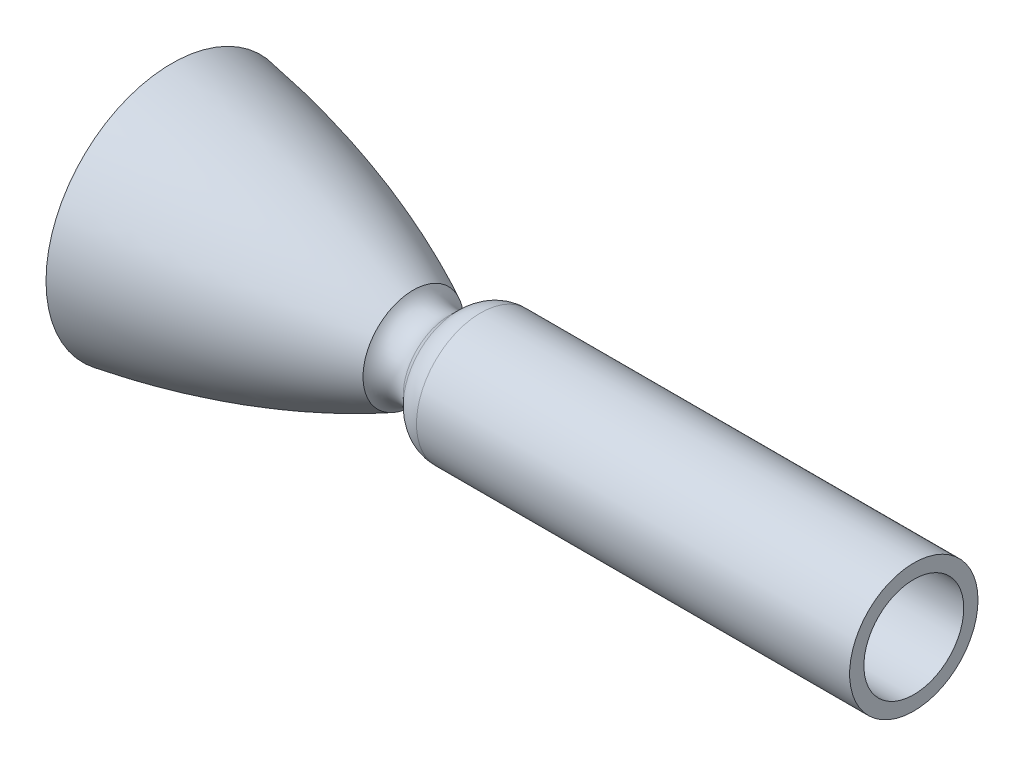
SolidWorks part; units mm, degrees
ref_plane "Front Plane" through (0, 0, 0) normal (0, 0, 1) x (1, 0, 0)
ref_plane "Top Plane" through (0, 0, 0) normal (0, 1, 0) x (1, 0, 0)
ref_plane "Right Plane" through (0, 0, 0) normal (1, 0, 0) x (0, 0, -1)
sketch "Sketch1" plane through (0, 0, 0) normal (0, 0, 1) x (1, 0, 0)
  line L0 (272.3324, 28) -> (29.4035, 28)
  line L1 (22.3324, 25.0711) -> (17.4121, 20.1508)
  line L3 (0, 0) -> (-234.9488, 0) construction
  line L8 (272.3324, 36) -> (29.4035, 36)
  line L12 (16.6756, 30.7279) -> (11.7553, 25.8076)
  line L13 (272.3324, 28) -> (272.3324, 36)
  line L14 (-145.1317, 62.6099) -> (-143.8678, 70.5094)
  arc A0 (29.4035, 28) -> (22.3324, 25.0711) centre (29.4035, 18) ccw
  arc A4 (29.4035, 36) -> (16.6756, 30.7279) centre (29.4035, 18) ccw
  arc A7 (-8.4641, 28.1148) -> (-8.4641, 28.1148) centre (-8.4641, 28.1148) ccw
  arc A8 (11.7553, 25.8076) -> (-8.4641, 28.1148) centre (2.5629, 35) cw construction
  arc A9 (-8.4641, 28.1148) -> (11.7553, 25.8076) centre (2.5629, 35) ccw
  arc A10 (-0.2556, 14.19) -> (0, 14.6541) centre (2.9733, 12.7139) cw construction
  arc A11 (17.4121, 20.1508) -> (-0.2556, 14.19) centre (2.5629, 35) cw construction
  arc A12 (17.4121, 20.1508) -> (2.5629, 14) centre (2.5629, 35) cw
  arc A13 (2.5629, 14) -> (0, 14.6541) centre (2.5629, 19.348) cw
  spline S0 degree 2 poles (0, 14.6541) (-64.0809, 49.6422) (-145.1317, 62.6099) knots 0 0 0 1 1 1 construction
  spline S1 degree 1 poles (-8.4641, 28.1148) (-143.8678, 70.5094) knots 0 0 1 1 construction
  spline S2 degree 2 poles (0, 14.6541) (-64.0809, 49.6422) (-145.1317, 62.6099) knots 0 0 0 1 1 1
  spline S3 degree 2 poles (-8.4641, 28.1148) (-69.2572, 58.5916) (-143.8678, 70.5094) knots 0.092893 0.092893 0.092893 1 1 1
  dimension "D1" = 10
  dimension "D4" = 21
  dimension "D5" = 5.348
  dimension "D14" = 28
  dimension "D16" = 250
  dimension "D2" = 14
  dimension "D6" = 45
  dimension "D7" = 62.6099
  dimension "D3" = 8
revolve "Revolve1" add sketch "Sketch1" angle 360 about L3 region at (150.868, 32.2127, 0)
equation "\"theta_t\"= 36.9009 - ( 426.271 / ( \"Aet\" + 7.00037 ) ) + ( 10026.8 / ( \"Aet\" + 7.00037 ) ^ 2 ) - ( 175410 / ( \"Aet\" + 7.00037 ) ^ 3 ) + ( ( 1.6742 * ( 10 ^ 6 ) ) / ( \"Aet\" + 7.00037 ) ^ 4 ) - ( ( 6.7643 * ( 10 ^ 6 ) ) / ( \"Aet\" + 7.00037 ) ^ 5 )"
equation "\"rt\"= 14"
equation "\"re\"= sqr ( \"rt\" ^ 2 * \"Aet\" )"
equation "\"Aet\"= 20"
equation "\"L\"= 0.8 * ( ( \"re\" / tan ( 15 ) ) - ( \"rt\" / tan ( 15 ) ) )"
equation "\"lc\"= ( \"l*\" / \"cr\" )"
equation "\"b\"= tan ( \"theta_t\" )"
equation "\"a\"= ( \"re\" - \"b\" * \"L\" - \"c\" ) / \"L\" ^ 2"
equation "\"c\"= \"rt\" * ( 1.382 - 0.382 * cos ( \"theta_t\" ) )"
equation "\"cr\"= 4"
equation "\"rc\"= sqr ( \"cr\" * ( \"rt\" ^ 2 ) )"
equation "\"D14@Sketch1\"=\"rc\""
equation "\"l*\"= 1000"
equation "\"D16@Sketch1\"=\"lc\""
equation "\"th\"= 8"
equation "\"theta_cr\"= 45deg"
equation "\"theta_e\"= 5.48 + ( 134.316 / ( \"Aet\" + 1.49269 ) ) - ( 1742.02 / ( \"Aet\" + 1.49269 ) ^ 2 ) + ( 13091 / ( \"Aet\" + 1.49269 ) ^ 3 ) - ( 41929.9 / ( \"Aet\" + 1.49269 ) ^ 4 ) + ( 44445.1 / ( \"Aet\" + 1.49269 ) ^ 5 )"
equation "\"Nx\"= 0"
equation "\"Ny\"= \"c\""
equation "\"Qx\"= ( \"re\" - ( tan ( \"theta_e\" ) * \"L\" ) - \"c\" ) / ( tan ( \"theta_t\" ) - tan ( \"theta_e\" ) )"
equation "\"Qy\"= tan ( \"theta_t\" ) * \"Qx\" + \"c\""
equation "\"Ex\"= \"L\""
equation "\"Ey\"= \"re\""
equation "\"D3@Sketch1\"=\"th\""
equation "\"D2@Sketch1\"=\"rt\""
equation "\"D4@Sketch1\"=\"rt\"*1.5"
equation "\"D5@Sketch1\"=\"rt\"*0.382"
equation "\"D6@Sketch1\"=\"theta_cr\""
equation "\"D7@Sketch1\"=\"re\""
